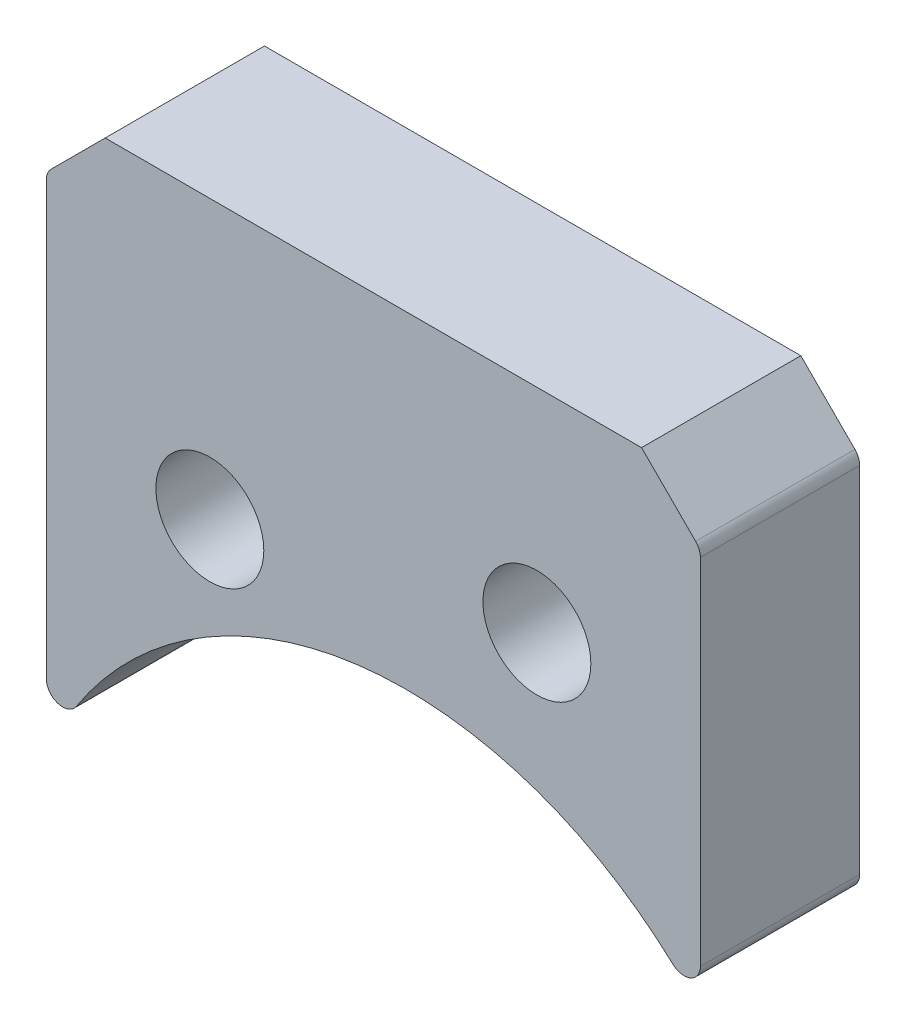
SolidWorks part; units mm, degrees
ref_plane "Front Plane" through (0, 0, 0) normal (0, 0, 1) x (1, 0, 0)
ref_plane "Top Plane" through (0, 0, 0) normal (0, 1, 0) x (1, 0, 0)
ref_plane "Right Plane" through (0, 0, 0) normal (1, 0, 0) x (0, 0, -1)
sketch "Sketch1" plane through (0, 0, 0) normal (0, 0, 1) x (1, 0, 0)
  line L0 (-20, 0) -> (0, 0)
  line L2 (-20, -17.2042) -> (-20, 0)
  line L4 (0, -14.0627) -> (0, 0)
  arc A0 (0, -14.0627) -> (-20, -17.2042) centre (-9, -22) ccw
  circle A1 centre (-15, -8.5) radius 1.65
  circle A2 centre (-5, -6.5) radius 1.65
  point P3 (0, 0)
  point P4 (0, -20.2826)
  point P5 (0, 0)
  point P7 (0, 0)
  point P11 (0, -22)
  point P12 (0, 0)
  point P16 (14.9575, -4.9959)
  point P17 (7.0863, -4.9959)
  point P18 (0, 0)
  point P19 (0, 0)
  dimension "D4" = 22
  dimension "10.5" = 12
  dimension "D2" = 3.3
  dimension "D1" = 9
  dimension "D3" = 20
  dimension "D5" = 5
  dimension "D6" = 15
  dimension "D7" = 6.5
  dimension "D8" = 8.5
extrude "Boss-Extrude1" add sketch "Sketch1" along normal blind 4.87
chamfer "Chamfer1" distance 1.8 angle 45 2 edges at (0, 0, 2.435) (-20, 0, 2.435)
fillet "Fillet1" radius 0.5 4 edges at (-20, -1.8, 2.435) (0, -1.8, 2.435) (0, -14.0627, 2.435) (-20, -17.2042, 2.435)
